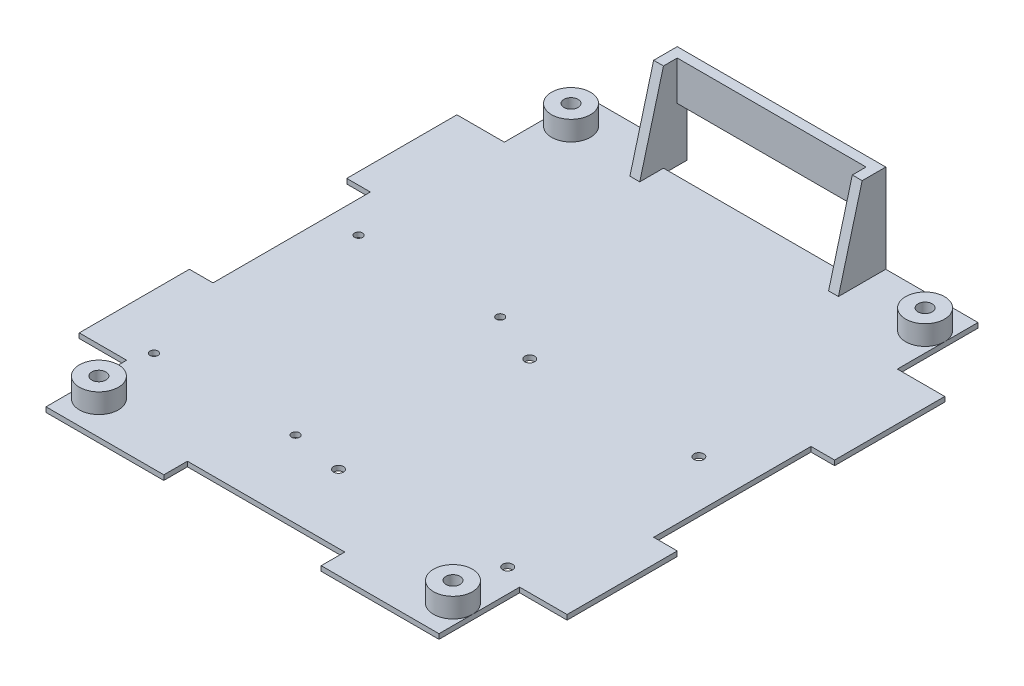
SolidWorks part; units mm, degrees
ref_plane "Front Plane" through (0, 0, 0) normal (0, 0, 1) x (1, 0, 0)
ref_plane "Top Plane" through (0, 0, 0) normal (0, 1, 0) x (1, 0, 0)
ref_plane "Right Plane" through (0, 0, 0) normal (1, 0, 0) x (0, 0, -1)
sketch "Sketch1" plane through (0, 0, 0) normal (0, 1, 0) x (1, 0, 0)
  line L0 (-25.4, 86.995) -> (-63.4314, 86.995)
  line L1 (-88.9, -101.6) -> (88.9, -101.6) construction
  line L2 (101.6, -88.9) -> (101.6, 88.9) construction
  line L3 (88.9, 101.6) -> (-88.9, 101.6) construction
  line L4 (-78.74, -60.96) -> (-63.4314, -60.96)
  line L5 (-63.4314, -60.96) -> (-63.4314, -86.995)
  line L6 (-63.4314, -86.995) -> (-25.4, -86.995)
  line L7 (63.4314, -86.995) -> (63.4314, -60.96)
  line L8 (63.4314, -60.96) -> (78.74, -60.96)
  line L9 (78.74, -60.96) -> (78.74, -25.4)
  line L10 (78.74, 60.96) -> (63.4314, 60.96)
  line L11 (63.4314, 60.96) -> (63.4314, 86.995)
  line L12 (63.4314, 86.995) -> (25.4, 86.995)
  line L13 (-63.4314, 86.995) -> (-63.4314, 60.96)
  line L14 (-63.4314, 60.96) -> (-78.74, 60.96)
  line L15 (-78.74, 60.96) -> (-78.74, 25.4)
  line L16 (-78.74, -25.4) -> (-78.74, -60.96)
  line L17 (-78.74, -25.4) -> (-71.12, -25.4)
  line L19 (-78.74, 25.4) -> (-71.12, 25.4)
  line L20 (-71.12, -25.4) -> (-71.12, 25.4)
  line L22 (-25.4, 86.995) -> (-25.4, 79.375)
  line L23 (-25.4, 79.375) -> (25.4, 79.375)
  line L24 (25.4, 86.995) -> (25.4, 79.375)
  line L25 (78.74, 25.4) -> (71.12, 25.4)
  line L27 (78.74, -25.4) -> (71.12, -25.4)
  line L28 (71.12, 25.4) -> (71.12, -25.4)
  line L30 (25.4, -86.995) -> (25.4, -79.375)
  line L31 (25.4, -79.375) -> (-25.4, -79.375)
  line L32 (-25.4, -86.995) -> (-25.4, -79.375)
  line L33 (78.74, 25.4) -> (78.74, 60.96)
  line L34 (25.4, -86.995) -> (63.4314, -86.995)
  line L35 (-101.6, 88.9) -> (-101.6, -88.9) construction
  arc A0 (88.9, -101.6) -> (101.6, -88.9) centre (88.9, -88.9) ccw construction
  arc A1 (-101.6, -88.9) -> (-88.9, -101.6) centre (-88.9, -88.9) ccw construction
  arc A2 (101.6, 88.9) -> (88.9, 101.6) centre (88.9, 88.9) ccw construction
  arc A3 (-101.6, 88.9) -> (-88.9, 101.6) centre (-88.9, 88.9) cw construction
  circle A4 centre (-57.15, 76.2) radius 2.286
  circle A5 centre (57.15, 76.2) radius 2.286
  circle A6 centre (57.15, -76.2) radius 2.286
  circle A7 centre (-57.15, -76.2) radius 2.286
  point P3 (0, 101.6)
  point P5 (101.6, 0)
  point P13 (101.6, 101.6)
  point P16 (-101.6, 101.6)
  point P38 (-71.12, 0)
  point P55 (0, -79.375)
  point P56 (0, 79.375)
  point P57 (71.12, 0)
  dimension "D2" = 12.7
  dimension "D11" = 4.572
  dimension "D8" = 44.45
  dimension "D1" = 203.2
  dimension "D3" = 203.2
  dimension "D4" = 22.86
  dimension "D5" = 15.3086
  dimension "D6" = 35.56
  dimension "D7" = 173.99
  dimension "D12" = 50.8
  dimension "D13" = 25.4
  dimension "D14" = 44.45
  dimension "D15" = 25.4
  dimension "D18" = 7.62
extrude "Main Body" add sketch "Sketch1" along normal blind 1.5875
sketch "Sketch9" plane through (0, 1.5875, 0) normal (0, 1, 0) x (1, 0, 0)
  line L0 (25.4, 79.375) -> (30.48, 79.375)
  line L1 (30.48, 79.375) -> (30.48, 86.995)
  line L2 (-25.4, 79.375) -> (-30.48, 79.375)
  line L3 (-30.48, 79.375) -> (-30.48, 86.995)
  line L43 (71.12, -25.4) -> (71.12, 25.4)
  line L44 (71.12, 25.4) -> (78.74, 25.4)
  line L45 (78.74, 25.4) -> (78.74, 60.96)
  line L46 (78.74, 60.96) -> (63.4314, 60.96)
  line L47 (63.4314, 60.96) -> (63.4314, 86.995)
  line L48 (63.4314, 86.995) -> (25.4, 86.995)
  line L49 (25.4, 86.995) -> (25.4, 79.375)
  line L50 (25.4, 79.375) -> (-25.4, 79.375)
  line L51 (-25.4, 79.375) -> (-25.4, 86.995)
  line L52 (-25.4, 86.995) -> (-63.4314, 86.995)
  line L53 (-63.4314, 86.995) -> (-63.4314, 60.96)
  line L54 (-63.4314, 60.96) -> (-78.74, 60.96)
  line L55 (-78.74, 60.96) -> (-78.74, 25.4)
  line L56 (-78.74, 25.4) -> (-71.12, 25.4)
  line L57 (-71.12, 25.4) -> (-71.12, -25.4)
  line L58 (-71.12, -25.4) -> (-78.74, -25.4)
  line L59 (-78.74, -25.4) -> (-78.74, -60.96)
  line L60 (-78.74, -60.96) -> (-63.4314, -60.96)
  line L61 (-63.4314, -60.96) -> (-63.4314, -86.995)
  line L62 (-63.4314, -86.995) -> (-25.4, -86.995)
  line L63 (-25.4, -86.995) -> (-25.4, -79.375)
  line L64 (-25.4, -79.375) -> (25.4, -79.375)
  line L65 (25.4, -79.375) -> (25.4, -86.995)
  line L66 (25.4, -86.995) -> (63.4314, -86.995)
  line L67 (63.4314, -86.995) -> (63.4314, -60.96)
  line L68 (63.4314, -60.96) -> (78.74, -60.96)
  line L69 (78.74, -60.96) -> (78.74, -25.4)
  line L70 (78.74, -25.4) -> (71.12, -25.4)
  line L83 (71.12, -25.4) -> (71.12, 25.4)
  line L84 (71.12, 25.4) -> (78.74, 25.4)
  line L85 (78.74, 25.4) -> (78.74, 60.96)
  line L86 (78.74, 60.96) -> (63.4314, 60.96)
  line L87 (63.4314, 60.96) -> (63.4314, 86.995)
  line L88 (63.4314, 86.995) -> (25.4, 86.995)
  line L89 (25.4, 86.995) -> (25.4, 79.375)
  line L90 (25.4, 79.375) -> (-25.4, 79.375)
  line L91 (-25.4, 79.375) -> (-25.4, 86.995)
  line L92 (-25.4, 86.995) -> (-63.4314, 86.995)
  line L93 (-63.4314, 86.995) -> (-63.4314, 60.96)
  line L94 (-63.4314, 60.96) -> (-78.74, 60.96)
  line L95 (-78.74, 60.96) -> (-78.74, 25.4)
  line L96 (-78.74, 25.4) -> (-71.12, 25.4)
  line L97 (-71.12, 25.4) -> (-71.12, -25.4)
  line L98 (-71.12, -25.4) -> (-78.74, -25.4)
  line L99 (-78.74, -25.4) -> (-78.74, -60.96)
  line L100 (-78.74, -60.96) -> (-63.4314, -60.96)
  line L101 (-63.4314, -60.96) -> (-63.4314, -86.995)
  line L102 (-63.4314, -86.995) -> (-25.4, -86.995)
  line L103 (-25.4, -86.995) -> (-25.4, -79.375)
  line L104 (-25.4, -79.375) -> (25.4, -79.375)
  line L105 (25.4, -79.375) -> (25.4, -86.995)
  line L106 (25.4, -86.995) -> (63.4314, -86.995)
  line L107 (63.4314, -86.995) -> (63.4314, -60.96)
  line L108 (63.4314, -60.96) -> (78.74, -60.96)
  line L109 (78.74, -60.96) -> (78.74, -25.4)
  line L110 (78.74, -25.4) -> (71.12, -25.4)
  line M55 (63.4314, 86.995) -> (25.4, 86.995)
  line M56 (25.4, 86.995) -> (25.4, 79.375)
  line M58 (-25.4, 79.375) -> (-25.4, 86.995)
  line M59 (-25.4, 86.995) -> (-63.4314, 86.995)
  dimension "D2" = 5.08
  dimension "D1" = 0
extrude "Cut-Extrude2" cut sketch "Sketch9" against normal up to next contours L0 L1 M55 M56 | L3 L2 M58 M59 region at (27.94, 1.5875, -83.185) region at (-27.94, 1.5875, -83.185)
sketch "Sketch10" plane through (0, 1.5875, 0) normal (0, 1, 0) x (1, 0, 0)
  line L0 (30.48, 79.375) -> (33.655, 79.375)
  line L1 (33.655, 79.375) -> (33.655, 86.995)
  line L2 (-30.48, 79.375) -> (-33.655, 79.375)
  line L3 (-33.655, 79.375) -> (-33.655, 86.995)
  line L40 (30.48, 86.995) -> (30.48, 79.375)
  line L41 (30.48, 79.375) -> (-30.48, 79.375)
  line L42 (-30.48, 79.375) -> (-30.48, 86.995)
  line L43 (-30.48, 86.995) -> (-63.4314, 86.995)
  line L44 (-63.4314, 86.995) -> (-63.4314, 60.96)
  line L45 (-63.4314, 60.96) -> (-78.74, 60.96)
  line L46 (-78.74, 60.96) -> (-78.74, 25.4)
  line L47 (-78.74, 25.4) -> (-71.12, 25.4)
  line L48 (-71.12, 25.4) -> (-71.12, -25.4)
  line L49 (-71.12, -25.4) -> (-78.74, -25.4)
  line L50 (-78.74, -25.4) -> (-78.74, -60.96)
  line L51 (-78.74, -60.96) -> (-63.4314, -60.96)
  line L52 (-63.4314, -60.96) -> (-63.4314, -86.995)
  line L53 (-63.4314, -86.995) -> (-25.4, -86.995)
  line L54 (-25.4, -86.995) -> (-25.4, -79.375)
  line L55 (-25.4, -79.375) -> (25.4, -79.375)
  line L56 (25.4, -79.375) -> (25.4, -86.995)
  line L57 (25.4, -86.995) -> (63.4314, -86.995)
  line L58 (63.4314, -86.995) -> (63.4314, -60.96)
  line L59 (63.4314, -60.96) -> (78.74, -60.96)
  line L60 (78.74, -60.96) -> (78.74, -25.4)
  line L61 (78.74, -25.4) -> (71.12, -25.4)
  line L62 (71.12, -25.4) -> (71.12, 25.4)
  line L75 (71.12, 25.4) -> (78.74, 25.4)
  line L76 (78.74, 25.4) -> (78.74, 60.96)
  line L77 (78.74, 60.96) -> (63.4314, 60.96)
  line L78 (63.4314, 60.96) -> (63.4314, 86.995)
  line L79 (63.4314, 86.995) -> (30.48, 86.995)
  line L80 (30.48, 86.995) -> (30.48, 79.375)
  line L81 (30.48, 79.375) -> (-30.48, 79.375)
  line L82 (-30.48, 79.375) -> (-30.48, 86.995)
  line L83 (-30.48, 86.995) -> (-63.4314, 86.995)
  line L84 (-63.4314, 86.995) -> (-63.4314, 60.96)
  line L85 (-63.4314, 60.96) -> (-78.74, 60.96)
  line L86 (-78.74, 60.96) -> (-78.74, 25.4)
  line L87 (-78.74, 25.4) -> (-71.12, 25.4)
  line L88 (-71.12, 25.4) -> (-71.12, -25.4)
  line L89 (-71.12, -25.4) -> (-78.74, -25.4)
  line L90 (-78.74, -25.4) -> (-78.74, -60.96)
  line L91 (-78.74, -60.96) -> (-63.4314, -60.96)
  line L92 (-63.4314, -60.96) -> (-63.4314, -86.995)
  line L93 (-63.4314, -86.995) -> (-25.4, -86.995)
  line L94 (-25.4, -86.995) -> (-25.4, -79.375)
  line L95 (-25.4, -79.375) -> (25.4, -79.375)
  line L96 (25.4, -79.375) -> (25.4, -86.995)
  line L97 (25.4, -86.995) -> (63.4314, -86.995)
  line L98 (63.4314, -86.995) -> (63.4314, -60.96)
  line L99 (63.4314, -60.96) -> (78.74, -60.96)
  line L100 (78.74, -60.96) -> (78.74, -25.4)
  line L101 (78.74, -25.4) -> (71.12, -25.4)
  line L102 (71.12, -25.4) -> (71.12, 25.4)
  line L115 (71.12, 25.4) -> (78.74, 25.4)
  line L116 (78.74, 25.4) -> (78.74, 60.96)
  line L117 (78.74, 60.96) -> (63.4314, 60.96)
  line L118 (63.4314, 60.96) -> (63.4314, 86.995)
  line L119 (63.4314, 86.995) -> (30.48, 86.995)
  line M43 (30.48, 86.995) -> (30.48, 79.375)
  line M45 (-30.48, 79.375) -> (-30.48, 86.995)
  line M46 (-30.48, 86.995) -> (-63.4314, 86.995)
  line M82 (63.4314, 86.995) -> (30.48, 86.995)
  dimension "D2" = 3.175
  dimension "D1" = 0
extrude "Boss-Extrude6" add sketch "Sketch10" along normal blind 28.575 contours L0 L1 M82 M43 | L3 L2 M45 M46 region at (32.0675, 1.5875, -83.185) region at (-32.0675, 1.5875, -83.185)
sketch "Sketch11" plane through (33.655, 0, 0) normal (1, 0, 0) x (0, 0, -1)
  line L0 (79.375, 30.1625) -> (71.7184, 1.5875)
  line L1 (71.7184, 1.5875) -> (79.375, 1.5875)
  line L4 (79.375, 1.5875) -> (86.995, 1.5875)
  line L5 (86.995, 1.5875) -> (86.995, 30.1625)
  line L6 (86.995, 30.1625) -> (79.375, 30.1625)
  line L7 (79.375, 30.1625) -> (79.375, 1.5875)
  line L8 (79.375, 1.5875) -> (86.995, 1.5875)
  line L9 (86.995, 1.5875) -> (86.995, 30.1625)
  line L10 (86.995, 30.1625) -> (79.375, 30.1625)
  line L11 (79.375, 30.1625) -> (79.375, 1.5875)
  line M9 (79.375, 30.1625) -> (79.375, 1.5875)
  dimension "D2" = 15
  dimension "D1" = 0
extrude "Boss-Extrude7" add sketch "Sketch11" against normal blind 3.175 contours L0 L1 M9 region at (33.655, 11.1125, -76.8228)
mirror "Mirror2" about plane through (0, 0, 0) normal (1, 0, 0) of "Boss-Extrude7"
sketch "Sketch12" plane through (0, 0, -86.995) normal (0, 0, -1) x (-1, 0, 0)
  line L0 (-30.48, 30.1625) -> (30.48, 30.1625)
  line L1 (-30.48, 17.4625) -> (30.48, 17.4625)
  line L6 (30.48, 30.1625) -> (30.48, 0)
  line L7 (30.48, 0) -> (63.4314, 0)
  line L8 (63.4314, 0) -> (63.4314, 1.5875)
  line L9 (63.4314, 1.5875) -> (33.655, 1.5875)
  line L10 (33.655, 1.5875) -> (33.655, 30.1625)
  line L11 (33.655, 30.1625) -> (30.48, 30.1625)
  line L12 (30.48, 30.1625) -> (30.48, 0)
  line L13 (30.48, 0) -> (63.4314, 0)
  line L14 (63.4314, 0) -> (63.4314, 1.5875)
  line L15 (63.4314, 1.5875) -> (33.655, 1.5875)
  line L16 (33.655, 1.5875) -> (33.655, 30.1625)
  line L17 (33.655, 30.1625) -> (30.48, 30.1625)
  line L18 (-63.4314, 0) -> (-30.48, 0)
  line L19 (-30.48, 0) -> (-30.48, 30.1625)
  line L20 (-30.48, 30.1625) -> (-33.655, 30.1625)
  line L21 (-33.655, 30.1625) -> (-33.655, 1.5875)
  line L22 (-33.655, 1.5875) -> (-63.4314, 1.5875)
  line L23 (-63.4314, 1.5875) -> (-63.4314, 0)
  line L24 (-63.4314, 0) -> (-30.48, 0)
  line L25 (-30.48, 0) -> (-30.48, 30.1625)
  line L26 (-30.48, 30.1625) -> (-33.655, 30.1625)
  line L27 (-33.655, 30.1625) -> (-33.655, 1.5875)
  line L28 (-33.655, 1.5875) -> (-63.4314, 1.5875)
  line L29 (-63.4314, 1.5875) -> (-63.4314, 0)
  line M15 (30.48, 30.1625) -> (30.48, 0)
  dimension "D3" = 12.7
  dimension "D1" = 0
  dimension "D2" = 0
extrude "Boss-Extrude8" add sketch "Sketch12" against normal blind 3.175 contours L25 L1 L0 M15 region at (0, 23.8125, -86.995)
sketch "Sketch5" plane through (0, 1.5875, 0) normal (0, 1, 0) x (1, 0, 0)
  line L0 (55.88, 4.445) -> (1.27, 4.445)
  line L1 (40.64, 67.945) -> (-40.64, 67.945)
  line L2 (40.64, 67.945) -> (40.64, 17.145)
  line L3 (40.64, 17.145) -> (-40.64, 17.145)
  line L4 (-40.64, 67.945) -> (-40.64, 17.145)
  line L5 (40.64, 67.945) -> (-40.64, 17.145) construction
  line L6 (40.64, 17.145) -> (-40.64, 67.945) construction
  line L8 (-60.96, -54.61) -> (-15.24, -54.61)
  line L9 (-60.96, -54.61) -> (-60.96, 11.43)
  line L10 (-60.96, 11.43) -> (-15.24, 11.43)
  line L11 (-15.24, -54.61) -> (-15.24, 11.43)
  line L36 (-30.48, 79.375) -> (-30.48, 71.7184)
  line L38 (30.48, 79.375) -> (-30.48, 79.375)
  line L40 (71.12, 25.4) -> (78.74, 25.4)
  line L41 (78.74, 25.4) -> (78.74, 60.96)
  line L42 (78.74, 60.96) -> (63.4314, 60.96)
  line L43 (63.4314, 60.96) -> (63.4314, 86.995)
  line L44 (63.4314, 86.995) -> (33.655, 86.995)
  line L45 (30.48, 79.375) -> (-30.48, 79.375)
  line L47 (-30.48, 79.375) -> (-30.48, 71.7184)
  line L49 (-63.4314, 86.995) -> (-63.4314, 60.96)
  line L50 (-63.4314, 60.96) -> (-78.74, 60.96)
  line L51 (-78.74, 60.96) -> (-78.74, 25.4)
  line L52 (-78.74, 25.4) -> (-71.12, 25.4)
  line L53 (-71.12, 25.4) -> (-71.12, -25.4)
  line L54 (-71.12, -25.4) -> (-78.74, -25.4)
  line L55 (-78.74, -25.4) -> (-78.74, -60.96)
  line L56 (-78.74, -60.96) -> (-63.4314, -60.96)
  line L57 (-63.4314, -60.96) -> (-63.4314, -86.995)
  line L58 (-63.4314, -86.995) -> (-25.4, -86.995)
  line L61 (71.12, -25.4) -> (71.12, 25.4)
  line L62 (71.12, -25.4) -> (71.12, 25.4)
  line L63 (63.4314, -86.995) -> (63.4314, -60.96)
  line L64 (63.4314, -60.96) -> (78.74, -60.96)
  line L65 (78.74, -60.96) -> (78.74, -25.4)
  line L66 (78.74, -25.4) -> (71.12, -25.4)
  line L74 (71.12, 25.4) -> (78.74, 25.4)
  line L75 (78.74, 25.4) -> (78.74, 60.96)
  line L76 (78.74, 60.96) -> (63.4314, 60.96)
  line L77 (63.4314, 60.96) -> (63.4314, 86.995)
  line L78 (63.4314, 86.995) -> (33.655, 86.995)
  line L83 (-63.4314, 86.995) -> (-63.4314, 60.96)
  line L84 (-63.4314, 60.96) -> (-78.74, 60.96)
  line L85 (-78.74, 60.96) -> (-78.74, 25.4)
  line L86 (-78.74, 25.4) -> (-71.12, 25.4)
  line L87 (-71.12, 25.4) -> (-71.12, -25.4)
  line L88 (-71.12, -25.4) -> (-78.74, -25.4)
  line L89 (-78.74, -25.4) -> (-78.74, -60.96)
  line L90 (-78.74, -60.96) -> (-63.4314, -60.96)
  line L91 (-63.4314, -60.96) -> (-63.4314, -86.995)
  line L92 (-63.4314, -86.995) -> (-25.4, -86.995)
  line L97 (63.4314, -86.995) -> (63.4314, -60.96)
  line L98 (63.4314, -60.96) -> (78.74, -60.96)
  line L99 (78.74, -60.96) -> (78.74, -25.4)
  line L100 (78.74, -25.4) -> (71.12, -25.4)
  line L107 (-33.655, 86.995) -> (-63.4314, 86.995)
  line L109 (-33.655, 86.995) -> (-63.4314, 86.995)
  line L110 (-25.4, -86.995) -> (-25.4, -79.375)
  line L111 (-25.4, -86.995) -> (-25.4, -79.375)
  line L112 (-25.4, -79.375) -> (25.4, -79.375)
  line L113 (-25.4, -79.375) -> (25.4, -79.375)
  line L114 (25.4, -79.375) -> (25.4, -86.995)
  line L115 (25.4, -79.375) -> (25.4, -86.995)
  line L116 (25.4, -86.995) -> (63.4314, -86.995)
  line L117 (25.4, -86.995) -> (63.4314, -86.995)
  line L130 (-30.48, 71.7184) -> (-33.655, 71.7184)
  line L131 (-30.48, 71.7184) -> (-33.655, 71.7184)
  line L132 (-33.655, 71.7184) -> (-33.655, 86.995)
  line L133 (-33.655, 71.7184) -> (-33.655, 86.995)
  line L150 (33.655, 86.995) -> (33.655, 71.7184)
  line L151 (33.655, 86.995) -> (33.655, 71.7184)
  line L152 (33.655, 71.7184) -> (30.48, 71.7184)
  line L153 (33.655, 71.7184) -> (30.48, 71.7184)
  line L154 (30.48, 71.7184) -> (30.48, 79.375)
  line L155 (30.48, 71.7184) -> (30.48, 79.375)
  circle A0 centre (1.27, 4.445) radius 1.5875
  circle A1 centre (55.88, 4.445) radius 1.5875
  circle A2 centre (55.88, -57.277) radius 1.5875
  circle A3 centre (1.27, -57.277) radius 1.5875
  circle A4 centre (-15.24, -54.61) radius 1.27
  circle A5 centre (-60.96, -54.61) radius 1.27
  circle A6 centre (-60.96, 11.43) radius 1.27
  circle A7 centre (-15.24, 11.43) radius 1.27
  text T0 "<b>LIPO</b>"
  point P0 (0, 42.545)
  point P2 (55.88, -57.277)
  point P4 (1.27, -57.277)
  point P6 (1.27, 4.445)
  point P8 (55.88, 4.445)
  point P25 (28.575, 4.445)
  point P40 (-15.24, -21.59)
  point P42 (-38.1, 11.43)
  point P44 (-38.1, -21.59)
  point P46 (0, 0)
  point P49 (0, 0)
  dimension "D8" = 3.175
  dimension "D9" = 3.175
  dimension "D10" = 3.175
  dimension "D11" = 3.175
  dimension "D17" = 2.54
  dimension "D2" = 54.61
  dimension "D3" = 12.7
  dimension "D4" = 81.28
  dimension "D5" = 61.722
  dimension "D6" = 50.8
  dimension "D7" = 19.05
  dimension "D12" = 21.59
  dimension "D13" = 28.575
  dimension "D14" = 28.575
  dimension "D15" = 45.72
  dimension "D16" = 66.04
  dimension "D18" = 21.59
  dimension "D19" = 38.1
  dimension "D1" = 0
sketch "Sketch13" plane through (0, 1.5875, 0) normal (0, 1, 0) x (1, 0, 0)
  line L32 (30.48, 79.375) -> (-30.48, 79.375)
  line L33 (-30.48, 79.375) -> (-30.48, 71.7184)
  line L34 (-30.48, 71.7184) -> (-33.655, 71.7184)
  line L35 (-33.655, 71.7184) -> (-33.655, 86.995)
  line L36 (-33.655, 86.995) -> (-63.4314, 86.995)
  line L37 (-63.4314, 86.995) -> (-63.4314, 60.96)
  line L38 (-63.4314, 60.96) -> (-78.74, 60.96)
  line L39 (-78.74, 60.96) -> (-78.74, 25.4)
  line L40 (-78.74, 25.4) -> (-71.12, 25.4)
  line L41 (-71.12, 25.4) -> (-71.12, -25.4)
  line L42 (-71.12, -25.4) -> (-78.74, -25.4)
  line L43 (-78.74, -25.4) -> (-78.74, -60.96)
  line L44 (-78.74, -60.96) -> (-63.4314, -60.96)
  line L45 (-63.4314, -60.96) -> (-63.4314, -86.995)
  line L46 (-63.4314, -86.995) -> (-25.4, -86.995)
  line L47 (-25.4, -86.995) -> (-25.4, -79.375)
  line L48 (-25.4, -79.375) -> (25.4, -79.375)
  line L49 (25.4, -79.375) -> (25.4, -86.995)
  line L50 (25.4, -86.995) -> (63.4314, -86.995)
  line L51 (63.4314, -86.995) -> (63.4314, -60.96)
  line L52 (63.4314, -60.96) -> (78.74, -60.96)
  line L53 (78.74, -60.96) -> (78.74, -25.4)
  line L54 (78.74, -25.4) -> (71.12, -25.4)
  line L55 (71.12, -25.4) -> (71.12, 25.4)
  line L56 (71.12, 25.4) -> (78.74, 25.4)
  line L57 (78.74, 25.4) -> (78.74, 60.96)
  line L58 (78.74, 60.96) -> (63.4314, 60.96)
  line L59 (63.4314, 60.96) -> (63.4314, 86.995)
  line L60 (63.4314, 86.995) -> (33.655, 86.995)
  line L61 (33.655, 86.995) -> (33.655, 71.7184)
  line L62 (33.655, 71.7184) -> (30.48, 71.7184)
  line L63 (30.48, 71.7184) -> (30.48, 79.375)
  line L64 (30.48, 79.375) -> (-30.48, 79.375)
  line L65 (-30.48, 79.375) -> (-30.48, 71.7184)
  line L66 (-30.48, 71.7184) -> (-33.655, 71.7184)
  line L67 (-33.655, 71.7184) -> (-33.655, 86.995)
  line L68 (-33.655, 86.995) -> (-63.4314, 86.995)
  line L69 (-63.4314, 86.995) -> (-63.4314, 60.96)
  line L70 (-63.4314, 60.96) -> (-78.74, 60.96)
  line L71 (-78.74, 60.96) -> (-78.74, 25.4)
  line L72 (-78.74, 25.4) -> (-71.12, 25.4)
  line L73 (-71.12, 25.4) -> (-71.12, -25.4)
  line L74 (-71.12, -25.4) -> (-78.74, -25.4)
  line L75 (-78.74, -25.4) -> (-78.74, -60.96)
  line L76 (-78.74, -60.96) -> (-63.4314, -60.96)
  line L77 (-63.4314, -60.96) -> (-63.4314, -86.995)
  line L78 (-63.4314, -86.995) -> (-25.4, -86.995)
  line L79 (-25.4, -86.995) -> (-25.4, -79.375)
  line L80 (-25.4, -79.375) -> (25.4, -79.375)
  line L81 (25.4, -79.375) -> (25.4, -86.995)
  line L82 (25.4, -86.995) -> (63.4314, -86.995)
  line L83 (63.4314, -86.995) -> (63.4314, -60.96)
  line L84 (63.4314, -60.96) -> (78.74, -60.96)
  line L85 (78.74, -60.96) -> (78.74, -25.4)
  line L86 (78.74, -25.4) -> (71.12, -25.4)
  line L87 (71.12, -25.4) -> (71.12, 25.4)
  line L88 (71.12, 25.4) -> (78.74, 25.4)
  line L89 (78.74, 25.4) -> (78.74, 60.96)
  line L90 (78.74, 60.96) -> (63.4314, 60.96)
  line L91 (63.4314, 60.96) -> (63.4314, 86.995)
  line L92 (63.4314, 86.995) -> (33.655, 86.995)
  line L93 (33.655, 86.995) -> (33.655, 71.7184)
  line L94 (33.655, 71.7184) -> (30.48, 71.7184)
  line L95 (30.48, 71.7184) -> (30.48, 79.375)
  circle A0 centre (57.15, 76.2) radius 2.286 construction
  circle A1 centre (-57.15, 76.2) radius 2.286 construction
  circle A2 centre (-57.15, -76.2) radius 2.286 construction
  circle A3 centre (57.15, -76.2) radius 2.286 construction
  circle A4 centre (57.15, 76.2) radius 2.286
  circle A5 centre (-57.15, 76.2) radius 2.286
  circle A6 centre (-57.15, -76.2) radius 2.286
  circle A7 centre (57.15, -76.2) radius 2.286
  circle A8 centre (57.15, 76.2) radius 6.2814
  circle A9 centre (-57.15, -76.2) radius 6.2814
  circle A10 centre (-57.15, 76.2) radius 6.2814
  circle A11 centre (57.15, -76.2) radius 6.2814
  point P40 (-57.15, -76.2)
  point P46 (57.15, 76.2)
  point P52 (57.15, -76.2)
  point P58 (-57.15, 76.2)
  circle M45 centre (57.15, -76.2) radius 2.286
  circle M46 centre (-57.15, 76.2) radius 2.286
  circle M47 centre (57.15, 76.2) radius 2.286
  circle M48 centre (-57.15, -76.2) radius 2.286
  dimension "D1" = 0
extrude "Boss-Extrude9" add sketch "Sketch13" along normal blind 6.35 contours A11 M45 | A11 M45 | A9 M48 | A9 M48 | A10 M46 | A10 M46 | A8 M47 | A8 M47 region at (-57.15, 1.5875, -82.3038) region at (-57.15, 1.5875, 70.0962) region at (51.0462, 1.5875, 76.2) region at (51.0462, 1.5875, -76.2)
extrude "Cut-Extrude3" cut sketch "Sketch5" against normal up to next contours A2 | A3 | A0 | A1 | A4 | A5 | A6 | A7
